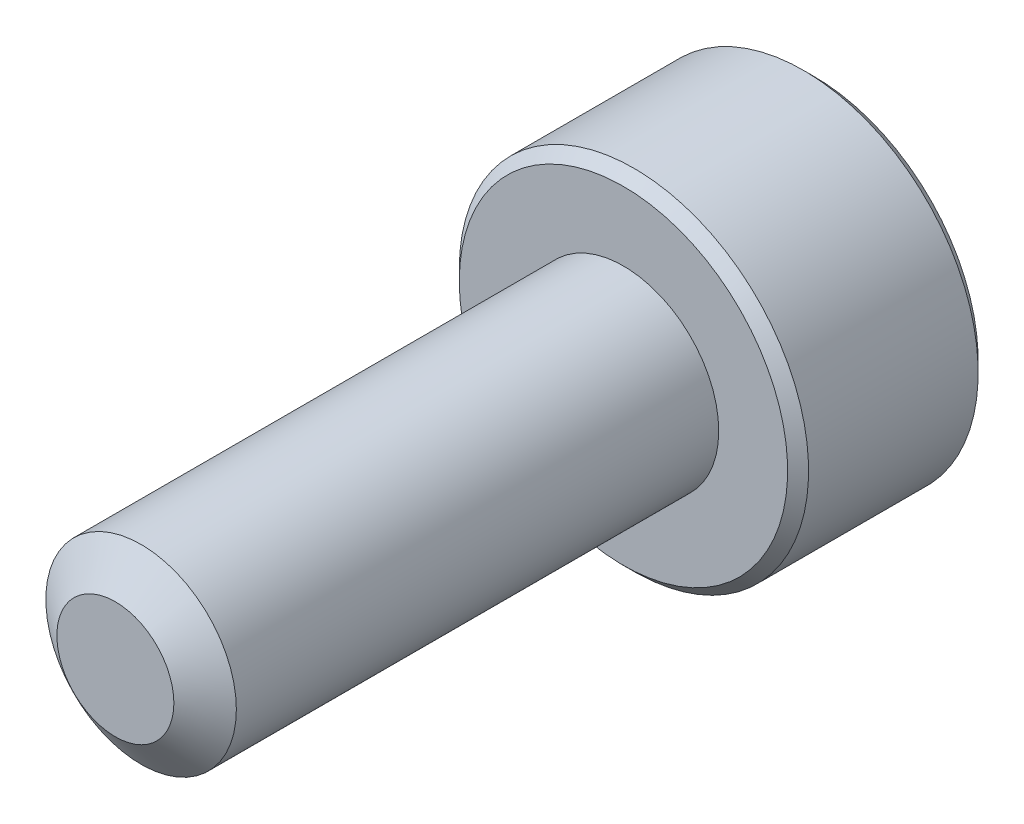
SolidWorks part; units mm, degrees
material "Alloy Steel"
ref_plane "Front Plane" through (0, 0, 0) normal (0, 0, 1) x (1, 0, 0)
ref_plane "Top Plane" through (0, 0, 0) normal (0, 1, 0) x (1, 0, 0)
ref_plane "Right Plane" through (0, 0, 0) normal (1, 0, 0) x (0, 0, -1)
sketch "Sketch1" plane through (0, 0, 0) normal (0, 0, 1) x (1, 0, 0)
  circle A0 centre (0, 0) radius 1.5
  dimension "OD" = 3
extrude "Extrude1" add sketch "Sketch1" against normal blind 8
sketch "Sketch2" plane through (0, 0, 0) normal (0, 0, 1) x (1, 0, 0)
  circle A0 centre (0, 0) radius 1.5 construction
  circle A1 centre (0, 0) radius 1.5
curve "Helix/Spiral1" [suppressed] pitch 0.5 height 8.5 turns 17 parameters "pitch"=0.5
sketch "Sketch3" plane through (0, 0, 0) normal (1, 0, 0) x (0, 0, -1)
  line L0 (-0.4375, 1.5) -> (-0.25, 1.1752)
  line L1 (-0.25, 1.1752) -> (-0.1875, 1.1752)
  line L2 (-0.1875, 1.1752) -> (0, 1.5)
  line L3 (-0.4375, 1.5) -> (0, 1.5)
  line L4 (-0.2187, 1.5) -> (-0.2187, 1.1752) construction
  line L5 (-0.3437, 1.3376) -> (-0.0937, 1.3376) construction
  line L6 (0, 1.5) -> (0, -1.5) construction
  line L7 (0, -1.5) -> (8, -1.5) construction
  point P11 (2.25, -1.5)
  dimension "D1" = 0.0625
  dimension "D2" = 0.25
  dimension "D3" = 60
  dimension "D4" = 2.25
sweep "Cut-Sweep1" [suppressed] cut profiles "Sketch3" path "Helix/Spiral1"
sketch "Sketch4" plane through (0, 0, 0) normal (1, 0, 0) x (0, 0, -1)
  line L0 (0.4053, 1.5) -> (0, 0.9212)
  line L1 (0, 0.9212) -> (0, 1.5)
  line L2 (0.4053, 1.5) -> (0, 1.5)
  line L3 (-0.4375, 1.5) -> (0, 1.5) construction
  line L4 (0, 0) -> (7.0209, 0) construction
  dimension "D1" = 55
  dimension "D2" = 0.254
revolve "Cut-Revolve1" cut sketch "Sketch4" angle 360 about L4
sketch "Sketch5" [suppressed] plane through (0, 0, 0) normal (1, 0, 0) x (0, 0, -1)
  line L0 (8, -1.1822) -> (8, 1.0703) construction
  line L1 (8, 1.5) -> (0.1203, 1.5)
  line L2 (8, 1.5) -> (8, 0)
  line L3 (8, 0) -> (0.0001, 0)
  line L4 (0.0001, 1.1698) -> (0.0001, 0)
  line L5 (0.1203, 1.5) -> (0.0001, 1.1698)
  line L6 (0, 0) -> (9.9695, 0) construction
  point P3 (0.0001, 1.5)
  point P10 (0.0001, 1.5)
  dimension "D1" = 0.3302
  dimension "Thread min" = 0.0001
  dimension "D3" = 20
revolve "partially thread" [suppressed] add sketch "Sketch5" angle 360 about L6
sketch "Sketch6" plane through (0, 0, -8) normal (0, 0, -1) x (-1, 0, 0)
  circle A0 centre (0, 0) radius 2.75
  dimension "head dia" = 5.5
extrude "Extrude2" add sketch "Sketch6" along normal blind 3
sketch "Sketch7" plane through (0, 0, -11) normal (0, 0, -1) x (-1, 0, 0)
  line L1 (0, 1.4434) -> (-1.25, 0.7217)
  line L2 (-1.25, 0.7217) -> (-1.25, -0.7217)
  line L3 (-1.25, -0.7217) -> (0, -1.4434)
  line L4 (0, -1.4434) -> (1.25, -0.7217)
  line L5 (1.25, -0.7217) -> (1.25, 0.7217)
  line L6 (1.25, 0.7217) -> (0, 1.4434)
  circle A0 centre (0, 0) radius 1.25 construction
  dimension "hex dia" = 2.5
extrude "Cut-Extrude1" cut sketch "Sketch7" against normal blind 1.875
sketch "Sketch8" plane through (0, 0, -11) normal (0, 0, -1) x (-1, 0, 0)
  circle A0 centre (0, 0) radius 1.4434
extrude "Cut-Extrude2" cut sketch "Sketch8" against normal through all draft 45
chamfer "Chamfer1" distance 0.165 angle 45 2 edges at (-2.75, 0, -11) (-2.75, 0, -8)
sketch "Sketch9" plane through (0, 0, 0) normal (1, 0, 0) x (0, 0, -1)
  line L0 (0, 1.5) -> (0, -1.5) construction
  line L1 (2.75, 1.5) -> (2.75, -1.5) construction
  dimension "D1" = 2.75
sketch "Sketch10" plane through (0, 0, 0) normal (1, 0, 0) x (0, 0, -1)
  line L0 (8, 1.5) -> (8, 0)
  line L1 (8, 1.5) -> (7.875, 1.5)
  line L2 (7.875, 1.5) -> (7.2537, 0)
  line L3 (8, 0) -> (7.2537, 0)
  line L4 (8, 2.585) -> (8, -2.585) construction
  dimension "D1" = 22.5
  dimension "D2" = 0.125
revolve "Revolve1" [suppressed] add sketch "Sketch10" angle 360 about L3
equation "\"D3@Helix/Spiral1\" = \"screw length@Extrude1\"+\"pitch@Helix/Spiral1\""
equation "\"D1@Sketch3\" = \"pitch@Helix/Spiral1\"*.125"
equation "\"D2@Sketch3\" = \"pitch@Helix/Spiral1\"*.5"
equation "\"D1@Cut-Extrude1\" = \"hex dia@Sketch7\"*.75"
equation "\"D1@Chamfer1\" = \"head dia@Sketch6\"*.03"
equation "\"D1@Sketch9\" = \"pitch@Helix/Spiral1\"*5.5"
equation "\"D2@Sketch10\" = \"pitch@Helix/Spiral1\"*.25"
equation "\"D4@Sketch3\" = \"pitch@Helix/Spiral1\"*4.50"
